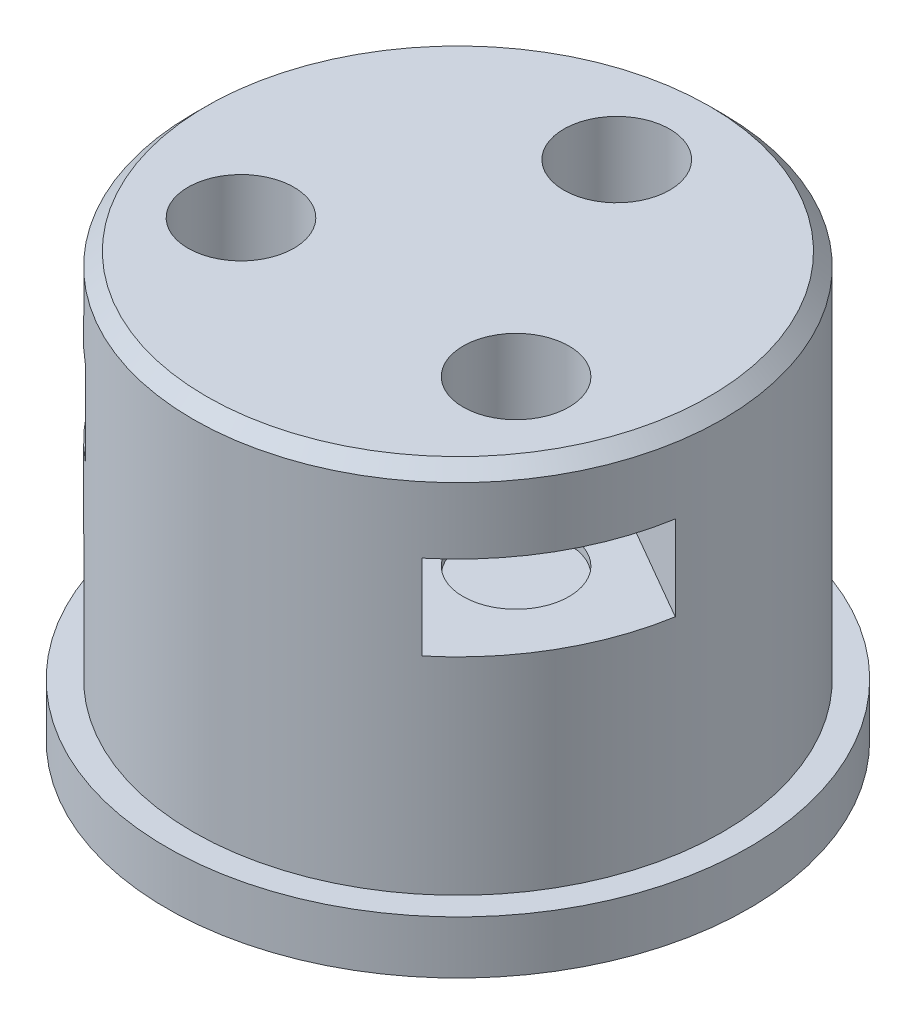
SolidWorks part; units mm, degrees
material "PLA"
ref_plane "Front Plane" through (0, 0, 0) normal (0, 0, 1) x (1, 0, 0)
ref_plane "Top Plane" through (0, 0, 0) normal (0, 1, 0) x (1, 0, 0)
ref_plane "Right Plane" through (0, 0, 0) normal (1, 0, 0) x (0, 0, -1)
sketch "Sketch1" plane through (0, 0, 0) normal (0, 1, 0) x (1, 0, 0)
  circle A0 centre (0, 0) radius 10
  circle A1 centre (0, 0) radius 8 construction
  dimension "D1" = 20
  dimension "D2" = 16
extrude "Boss-Extrude1" add sketch "Sketch1" along normal blind 16
sketch "Sketch2" plane through (0, 0, 0) normal (0, -1, 0) x (1, 0, 0)
  circle A0 centre (0, 0) radius 10 construction
  circle A1 centre (0, 0) radius 10
  circle A2 centre (0, 0) radius 11
extrude "Boss-Extrude2" add sketch "Sketch2" against normal blind 2
sketch "Sketch3" plane through (0, 0, 0) normal (0, -1, 0) x (1, 0, 0)
  circle A0 centre (0, 0) radius 8
  dimension "D1" = 16
extrude "Cut-Extrude1" cut sketch "Sketch3" against normal blind 6.5
sketch "Sketch4" plane through (0, 16, 0) normal (0, 1, 0) x (1, 0, 0)
  circle A0 centre (0, 0) radius 6 construction
  circle A1 centre (0, 6) radius 2
  circle A2 centre (5.1962, -3) radius 2
  circle A3 centre (-5.1962, -3) radius 2
  point P14 (0, 0)
  dimension "D1" = 12
  dimension "D2" = 4
  dimension "D3" = 3
extrude "Cut-Extrude2" cut sketch "Sketch4" against normal blind 6.5
sketch "Sketch5" plane through (0, 16, 0) normal (0, 1, 0) x (1, 0, 0)
  line L0 (-3.5, 8.0207) -> (-3.5, 9.3675)
  line L1 (0, 1.9585) -> (3.5, 3.9793)
  line L2 (3.5, 3.9793) -> (3.5, 8.0207)
  line L3 (3.5, 8.0207) -> (0, 10.0415)
  line L4 (0, 10.0415) -> (-3.5, 8.0207)
  line L5 (-3.5, 8.0207) -> (-3.5, 3.9793)
  line L6 (-3.5, 3.9793) -> (0, 1.9585)
  line L7 (3.5, 8.0207) -> (3.5, 9.3675)
  line L8 (8.6962, -0.9793) -> (9.8625, -1.6527)
  line L9 (8.6962, -0.9793) -> (5.1962, 1.0415)
  line L10 (8.6962, -5.0207) -> (8.6962, -0.9793)
  line L11 (5.1962, -7.0415) -> (8.6962, -5.0207)
  line L12 (5.1962, -7.0415) -> (6.3625, -7.7148)
  line L13 (1.6962, -5.0207) -> (5.1962, -7.0415)
  line L14 (1.6962, -0.9793) -> (1.6962, -5.0207)
  line L15 (5.1962, 1.0415) -> (1.6962, -0.9793)
  line L16 (-5.1962, -7.0415) -> (-6.3625, -7.7148)
  line L17 (-5.1962, -7.0415) -> (-1.6962, -5.0207)
  line L18 (-8.6962, -5.0207) -> (-5.1962, -7.0415)
  line L19 (-8.6962, -0.9793) -> (-8.6962, -5.0207)
  line L20 (-8.6962, -0.9793) -> (-9.8625, -1.6527)
  line L21 (-5.1962, 1.0415) -> (-8.6962, -0.9793)
  line L22 (-1.6962, -0.9793) -> (-5.1962, 1.0415)
  line L23 (-1.6962, -5.0207) -> (-1.6962, -0.9793)
  circle A0 centre (0, 6) radius 3.5 construction
  circle A1 centre (0, 0) radius 6 construction
  circle A3 centre (-5.1962, -3) radius 2
  circle A4 centre (-5.1962, -3) radius 2
  circle A5 centre (5.1962, -3) radius 2
  circle A6 centre (5.1962, -3) radius 2
  circle A7 centre (0, 6) radius 2
  circle A8 centre (0, 6) radius 2
  circle A9 centre (0, 0) radius 10 construction
  circle A10 centre (0, 0) radius 10
  point P50 (0, 0)
  circle M11 centre (0, 6) radius 2
  circle M12 centre (5.1962, -3) radius 2
  circle M13 centre (-5.1962, -3) radius 2
  circle M15 centre (0, 0) radius 10
  dimension "D5" = 7
  dimension "D4" = 0
  dimension "D6" = 3
extrude "Cut-Extrude3" cut sketch "Sketch5" against normal blind 3.2 from offset 3 contours L18 L16 M15 | L17 L23 L22 L21 L19 L18 M15 M13 | L19 L20 M15 | L5 L6 L1 L2 L3 L4 M15 M11 | L4 L0 M15 | L3 L7 M15 | L10 L8 M15 | L9 L15 L14 L13 L11 L10 M15 M12 | L11 L12 M15 region at (-2.2825, 16, -9.2115) region at (-1.7328, 16, -8.9179) region at (-9.1186, 16, 2.629) region at (2.2825, 16, -9.2115) region at (-6.8927, 16, 0.0615) region at (-6.8361, 16, 6.5825) region at (9.1186, 16, 2.629) region at (6.8361, 16, 6.5825) region at (8.5892, 16, 2.9583) offset against normal yes
sketch "Sketch6" plane through (0, 0, 0) normal (0, -1, 0) x (1, 0, 0)
  circle A0 centre (0, 0) radius 8
  circle A1 centre (0, 0) radius 7
  circle A2 centre (0, 0) radius 8 construction
extrude "Boss-Extrude3" add sketch "Sketch6" against normal up to surface (6.5 mm away) from offset 5 up to face at (0, 6.5, -8) offset against normal yes
chamfer "Chamfer1" distance 0.5 angle 45 1 edges at (0, 16, 10)
equation "\"Ns\" = 80"
equation "\"Np_b\" = 55"
equation "\"Np_s\" = 35"
equation "\"Nr_b\" = 190"
equation "\"module\" = 0.5"
equation "\"pressure_angle\" = 20.0"
equation "\"h_a\" = 0.5"
equation "\"h_f\" = 0.625"
equation "\"clr_tip_root\" = 0.125"
equation "\"dp_r_b\" = 95.0"
equation "\"db_r_b\" = 89.2707989746613"
equation "\"fw_r_b\" = 21.365107882670422"
equation "\"alpha_r_b\" = 0.8539582918412414"
equation "\"beta_r_b\" = 2.655285004735114"
equation "\"bearing_ID\" = 75"
equation "\"bearing_OD\" = 95"
equation "\"bearing_height\" = 10"
equation "\"clearance_planet\" = 1.5"
equation "\"case_dist\" = 6.5"
equation "\"Motor_case_OD_max\" = 131.3"
equation "\"case_mounting_PCD\" = 123.8"
equation "\"bearing mount thickness\" = 8"
equation "\"case_mounting_hole_dia\" = 3"
equation "\"output_mounting_PCD\" = 103"
equation "\"output_mounting_hole_dia\" = 4"
equation "\"clearance_case_mount_holes_shell_thickness\" = 1"
equation "\"motor_case_OD_base\" = 121.8"
equation "\"sec_carrier_thickness\" = 5"
equation "\"sun_coupler_hub_thickness\" = 4"
equation "\"clearance_sun_coupler_sec_carrier\" = 1.5"
equation "\"clearance_motor_and_case\" = 5"
equation "\"motor_OD\" = 106.8"
equation "\"Motor_case_thickness\" = 2.5"
equation "\"Motor_case_ID\" = 116.8"
equation "\"case_mounting_hole_shift\" = 1.0"
equation "\"output_mounting_nut_wrench_size\" = 7"
equation "\"output_mounting_nut_thickness\" = 3.2"
equation "\"case_mounting_hole_allen_socket_dia\" = 5.5"
equation "\"output_mounting_nut_depth\" = 3"
equation "\"case_mounting_bolt_depth\" = 4.5"
equation "\"ring_radial_thickness\" = 5"
equation "\"ring_OD_b\" = 105.0"
equation "\"ring_to_chamfer_clearance\" = 1.5"
equation "\"Motor_case_OD_base_to_chamfer\" = 5"
equation "\"pattern_offset_from_motor_case_OD_base\" = 3"
equation "\"pattern_bulge_dia\" = 3"
equation "\"pattern_num_bulge\" = 18"
equation "\"pattern_depth\" = 2"
equation "\"motor_height\" = 47.6"
equation "\"case_mounting_wrench_size\" = 5.5"
equation "\"case_mounting_nut_clearance\" = 2"
equation "\"base_plate_thickness\" = 4"
equation "\"case_mounting_nut_thickness\" = 2.4"
equation "\"case_mounting_surface_height\" = 4"
equation "\"motor_mount_hole_PCD\" = 40"
equation "\"motor_mount_hole_dia\" = 5"
equation "\"motor_mount_hole_num\" = 4"
equation "\"central_hole_offset_from_motor_mount_PCD\" = 5"
equation "\"wire_slot_dist_from_center\" = 45.5"
equation "\"wire_slot_length\" = 10"
equation "\"wire_slot_radius\" = 3"
equation "\"driver_upper_holes_dist_from_center\" = 29"
equation "\"driver_lower_holes_dist_from_center\" = 13"
equation "\"driver_side_holes_dist_from_center\" = 22.5"
equation "\"driver_mount_holes_dia\" = 3"
equation "\"driver_mount_inserts_OD\" = 4.8"
equation "\"driver_mount_thickness\" = 1.5"
equation "\"driver_mount_height\" = 6"
equation "\"air_flow_hole_offset\" = 3"
equation "\"pressure angle\" = 20.0"
equation "\"h_b\" = 0.625"
equation "\"fw_p_s\" = 15.81085678360617"
equation "\"num_planet\" = 5"
equation "\"planet_pin_bolt_dia\" = 5"
equation "\"planet_pin_socket_head_dia\" = 8.5"
equation "\"carrier_PCD\" = 67.5"
equation "\"planet_shaft_dia\" = 8"
equation "\"planet_shaft_step_offset\" = 1"
equation "\"carrier_trapezoidal_support_sun_offset\" = 5"
equation "\"carrier_trapezoidal_support_hole_PCD_offset_bearing_ID\" = 4"
equation "\"carrier_trapezoidal_support_hole_dia\" = 3"
equation "\"carrier_trapezoidal_support_hole_socket_head_dia\" = 5.5"
equation "\"carrier_bearing_step_width\" = 1.5"
equation "\"standard_clearance_1_5mm\" = 1.5"
equation "\"standard_fillet_1_5mm\" = 1.5"
equation "\"sun_shaft_bearing_OD\" = 16"
equation "\"sun_shaft_bearing_width\" = 5"
equation "\"standard_bearing_insertion_chamfer\" = 0.5"
equation "\"carrier_trapezoidal_support_hole_wrench_size\" = 5.5"
equation "\"planet_pin_bolt_wrench_size\" = 8"
equation "\"planet_bearing_OD\" = 12"
equation "\"planet_bearing_width\" = 3.5"
equation "\"planet_bore\" = 10"
equation "\"motor_output_hole_PCD\" = 23"
equation "\"motor_output_hole_dia\" = 4"
equation "\"motor_output_hole_num\" = 4"
equation "\"dp_s\" = 40.0"
equation "\"db_s\" = 37.58770483143634"
equation "\"fw_s_calc\" = 4.872946430626146"
equation "\"alpha_s\" = 0.8539582918412272"
equation "\"beta_s\" = 0.5420834163175456"
equation "\"dp_p_b\" = 27.5"
equation "\"db_p_b\" = 25.84154707161248"
equation "\"alpha_p_b\" = 0.8539582918412449"
equation "\"beta_p_b\" = 1.564810689044783"
equation "\"sun_shaft_bearing_ID\" = 8"
equation "\"sun_hub_dia\" = 30.0"
equation "\"sun_central_bolt_dia\" = 5"
equation "\"sun_central_bolt_socket_head_dia\" = 8.5"
equation "\"fw_s_used\" = 44.67596466627659"
equation "\"motor_output_hole_CSK_OD\" = 8"
equation "\"motor_output_hole_CSK_head_height\" = 2.0"
equation "\"bearing_retainer_thickness\" = 2"
equation "\"fw_p_b\" = 21.365107882670422"
equation "\"dp_p_s\" = 17.5"
equation "\"db_p_s\" = 16.444620863753396"
equation "\"alpha_p_s\" = 0.8539582918412556"
equation "\"beta_p_s\" = 3.434940559174632"
equation "\"Nr_s\" = 170"
equation "\"clr_tip_root_s\" = 0.125"
equation "\"dp_r_s\" = 85.0"
equation "\"db_r_s\" = 79.87387276680222"
equation "\"fw_r_s\" = 14.31085678360617"
equation "\"alpha_r_s\" = 0.8539582918412307"
equation "\"beta_r_s\" = 2.766740113094226"
equation "\"D1@Boss-Extrude1\"=\"bearing_height\" + \"carrier_thickness\" + \"carrier_small_ring_inner_bearing_flap\""
equation "\"D1@Cut-Extrude1\"=\"sun_shaft_bearing_width\" + \"standard_clearance_1_5mm\""
equation "\"D5@Sketch5\"=\"small_ring_output_wall_to_bearing_shaft_attachement_nut_wrench\""
equation "\"small_ring_case_thickness\" = 4"
equation "\"carrier_thickness\" = 4"
equation "\"small_ring_output_wall_thickness\" = 5"
equation "\"small_ring_output_wall_to_bearing_shaft_attachement_hole_dia\" = 4"
equation "\"small_ring_output_wall_to_bearing_shaft_attachement_hole_pcd\" = 12"
equation "\"small_ring_output_wall_to_bearing_shaft_attachement_hole_num\" = 3"
equation "\"small_ring_output_wall_to_bearing_shaft_attachement_hole_CSK_OD\" = 8"
equation "\"small_ring_output_wall_to_bearing_shaft_attachement_hole_CSK_head_height\" = 2.0"
equation "\"carrier_small_ring_inner_bearing_ID\" = 20"
equation "\"carrier_small_ring_inner_bearing_OD\" = 32"
equation "\"carrier_small_ring_inner_bearing_height\" = 7"
equation "\"D1@Sketch1\"=\"carrier_small_ring_inner_bearing_ID\""
equation "\"D2@Sketch1\"=\"sun_shaft_bearing_OD\""
equation "\"D1@Sketch2\"=\"standard_clearance_1_5mm\"*2/3"
equation "\"D1@Sketch3\"=\"sun_shaft_bearing_OD\""
equation "\"D1@Sketch4\"=\"small_ring_output_wall_to_bearing_shaft_attachement_hole_pcd\""
equation "\"D2@Sketch4\"=\"small_ring_output_wall_to_bearing_shaft_attachement_hole_dia\""
equation "\"D3@Sketch4\"=\"small_ring_output_wall_to_bearing_shaft_attachement_hole_num\""
equation "\"D6@Sketch5\"=\"small_ring_output_wall_to_bearing_shaft_attachement_hole_num\""
equation "\"D19@Cut-Extrude3\"=\"standard_clearance_1_5mm\"*2"
equation "\"D1@Sketch6\"=\"standard_clearance_1_5mm\"*2/3"
equation "\"D19@Boss-Extrude3\"=\"sun_shaft_bearing_width\""
equation "\"small_ring_output_wall_to_bearing_shaft_attachement_hole_depth\" = 6.5"
equation "\"small_ring_output_wall_to_bearing_shaft_attachement_nut_wrench\" = 7"
equation "\"small_ring_output_wall_to_bearing_shaft_attachement_nut_thickness\" = 3.2"
equation "\"carrier_small_ring_inner_bearing_flap\" = 2"
equation "\"D1@Boss-Extrude2\"=\"carrier_small_ring_inner_bearing_flap\""
equation "\"D1@Cut-Extrude2\"=\"small_ring_output_wall_to_bearing_shaft_attachement_hole_depth\""
equation "\"D1@Cut-Extrude3\"=\"small_ring_output_wall_to_bearing_shaft_attachement_nut_thickness\""
equation "\"D1@Chamfer1\"=\"standard_bearing_insertion_chamfer\""
